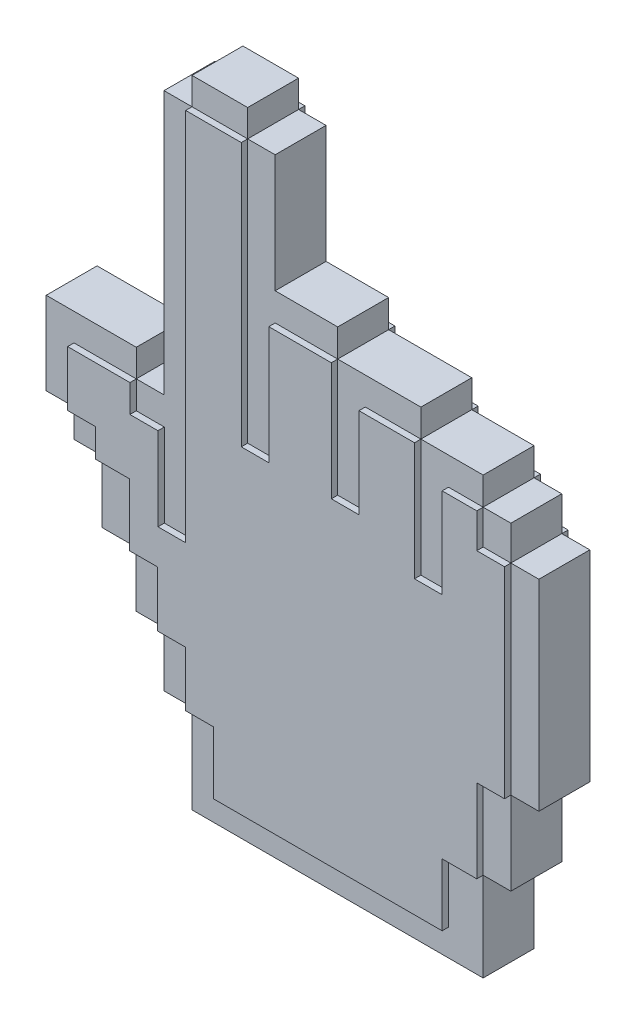
SolidWorks part; units mm, degrees
ref_plane "Front Plane" through (0, 0, 0) normal (0, 0, 1) x (1, 0, 0)
ref_plane "Top Plane" through (0, 0, 0) normal (0, 1, 0) x (1, 0, 0)
ref_plane "Right Plane" through (0, 0, 0) normal (1, 0, 0) x (0, 0, -1)
sketch "Sketch1" plane through (0, 0, 0) normal (0, 0, 1) x (1, 0, 0)
  line L0 (121.3333, 470) -> (606.6667, 470) construction
  line L1 (-21.3493, -53.5319) -> (-21.3493, -35.757)
  line L2 (-21.3493, -35.757) -> (-26.9344, -35.757)
  line L3 (-26.9344, -35.757) -> (-26.9344, -24.7744)
  line L4 (-26.9344, -24.7744) -> (-32.5196, -24.7744)
  line L5 (-32.5196, -24.7744) -> (-32.5196, -13.6979)
  line L6 (-32.5196, -13.6979) -> (-39.3251, -13.6979)
  line L7 (-39.3251, -13.6979) -> (-39.3251, -1.2604)
  line L8 (-39.3251, -1.2604) -> (-44.9102, -1.2604)
  line L9 (-44.9102, -1.2604) -> (-44.9102, 4.3717)
  line L10 (-44.9102, 4.3717) -> (-50.4546, 4.3717)
  line L11 (-50.4546, 4.3717) -> (-50.4546, 20.8885)
  line L12 (-50.4546, 20.8885) -> (-32.4738, 20.8885)
  line L13 (-32.4738, 20.8885) -> (-32.4738, 15.4225)
  line L14 (-32.4738, 15.4225) -> (-26.9344, 15.4225)
  line L15 (-26.9344, 15.4225) -> (-26.9344, 68.0248)
  line L16 (-26.9344, 68.0248) -> (-21.3493, 68.0248)
  line L17 (-21.3493, 68.0248) -> (-21.3493, 73.4488)
  line L18 (-21.3493, 73.4488) -> (-10.2409, 73.4488)
  line L19 (-10.2409, 73.4488) -> (-10.2409, 68.0248)
  line L20 (-10.2409, 68.0248) -> (-4.7518, 68.0248)
  line L21 (-4.7518, 68.0248) -> (-4.7518, 44.5101)
  line L22 (-4.7518, 44.5101) -> (7.7353, 44.5101)
  line L23 (7.7353, 44.5101) -> (7.7353, 38.9478)
  line L24 (7.7353, 38.9478) -> (24.3372, 38.9478)
  line L25 (24.3372, 38.9478) -> (24.3372, 33.4179)
  line L26 (24.3372, 33.4179) -> (36.7659, 33.4179)
  line L27 (36.7659, 33.4179) -> (36.7659, 27.862)
  line L28 (36.7659, 27.862) -> (42.3, 27.862)
  line L29 (42.3, 27.862) -> (42.3, 20.9709)
  line L30 (42.3, 20.9709) -> (47.8955, 20.9709)
  line L31 (47.8955, 20.9709) -> (47.8955, -19.1458)
  line L32 (47.8955, -19.1458) -> (42.3, -19.1458)
  line L33 (42.3, -19.1458) -> (42.3, -35.757)
  line L34 (42.3, -35.757) -> (36.7659, -35.757)
  line L35 (36.7659, -35.757) -> (36.7659, -53.5319)
  line L36 (36.7659, -53.5319) -> (-21.3493, -53.5319)
  line L37 (-15.7951, -48.1996) -> (29.8514, -48.1996)
  line L38 (29.8514, -48.1996) -> (29.8514, -35.757)
  line L39 (29.8514, -35.757) -> (36.7659, -35.757)
  line L40 (36.7659, -19.1458) -> (42.3, -19.1458)
  line L41 (42.3, -19.1458) -> (42.3, 20.9709)
  line L42 (36.7659, 20.9709) -> (36.7659, 27.862)
  line L43 (36.7659, 27.862) -> (29.8514, 27.862)
  line L44 (29.8514, 27.862) -> (29.8514, 9.898)
  line L45 (29.8514, 9.898) -> (24.3372, 9.898)
  line L46 (24.3372, 9.898) -> (24.3372, 33.4179)
  line L47 (24.3372, 33.4179) -> (13.2472, 33.4179)
  line L48 (13.2472, 33.4179) -> (13.2472, 15.4225)
  line L49 (13.2472, 15.4225) -> (7.7353, 15.4225)
  line L50 (7.7353, 15.4225) -> (7.7353, 38.9478)
  line L51 (7.7353, 38.9478) -> (-4.7518, 38.9478)
  line L52 (-4.7518, 38.9478) -> (-4.7518, 15.4225)
  line L53 (-4.7518, 15.4225) -> (-10.2409, 15.4225)
  line L54 (-10.2409, 15.4225) -> (-10.2409, 68.0248)
  line L55 (-21.3493, 68.0248) -> (-21.3493, -6.7133)
  line L56 (-21.3493, -6.7133) -> (-26.8748, -6.7133)
  line L57 (-26.8748, -6.7133) -> (-26.8748, 9.898)
  line L58 (-26.8748, 9.898) -> (-32.4738, 9.898)
  line L59 (-32.4738, 9.898) -> (-32.4738, 15.4225)
  line L60 (-32.4738, 15.4225) -> (-44.9102, 15.4225)
  line L61 (-44.9102, 15.4225) -> (-44.9102, 4.3717)
  line L62 (-44.9102, 4.3717) -> (-39.3251, 4.3717)
  line L63 (-39.3251, 4.3717) -> (-39.3251, -1.2604)
  line L64 (-39.3251, -1.2604) -> (-32.5196, -1.2604)
  line L65 (-32.5196, -1.2604) -> (-32.5196, -13.6979)
  line L66 (-32.5196, -13.6979) -> (-26.9344, -13.6979)
  line L67 (-26.9344, -13.6979) -> (-26.9344, -24.7744)
  line L68 (-26.9344, -24.7744) -> (-21.3493, -24.7744)
  line L69 (-21.3493, -24.7744) -> (-21.3493, -35.757)
  line L70 (-21.3493, -35.757) -> (-15.7951, -35.757)
  line L71 (-15.7951, -35.757) -> (-15.7951, -48.1996)
  line L72 (-21.3493, 68.0248) -> (-10.2409, 68.0248)
  line L73 (36.7659, -19.1458) -> (36.7659, -35.757)
  line L74 (36.7659, 20.9709) -> (42.3, 20.9709)
  point P44 (0, 0)
  dimension "D1" = 7.7353
  dimension "D2" = 13.2472
  dimension "D3" = 24.3372
  dimension "D4" = 29.8514
  dimension "D5" = 36.7659
  dimension "D6" = 42.3
  dimension "D7" = 47.8955
  dimension "D8" = 4.7518
  dimension "D9" = 10.2409
  dimension "D10" = 15.7951
  dimension "D11" = 21.3493
  dimension "D12" = 26.8748
  dimension "D13" = 26.9344
  dimension "D14" = 32.4738
  dimension "D15" = 39.3251
  dimension "D16" = 4.3717
  dimension "D17" = 9.898
  dimension "D18" = 50.4546
  dimension "D19" = 15.4225
  dimension "D20" = 20.8885
  dimension "D21" = 20.9709
  dimension "D22" = 27.862
  dimension "D23" = 33.4179
  dimension "D24" = 38.9478
  dimension "D25" = 44.5101
  dimension "D26" = 68.0248
  dimension "D27" = 73.4488
  dimension "D28" = 470
  dimension "D29" = 1.2604
  dimension "D30" = 6.7133
  dimension "D31" = 13.6979
  dimension "D32" = 19.1458
  dimension "D33" = 24.7744
  dimension "D34" = 35.757
  dimension "D35" = 48.1996
  dimension "D36" = 53.5319
extrude "Boss-Extrude1" add sketch "Sketch1" along normal mid plane 12.7 contours L74 L42 L43 L44 L45 L46 L47 L48 L49 L50 L51 L52 L53 L54 L72 L55 L56 L57 L58 L59 L60 L61 L62 L63 L64 L65 L66 L67 L68 L69 L70 L71 L37 L38 L39 L73 L40 L41 region at (3.6988, -2.9365, 0)
extrude "Boss-Extrude2" add sketch "Sketch1<4>" along normal mid plane 10.16 contours L61 L60 L13 L12 L11 L10 | L63 L62 L9 L8 | L65 L64 L7 L6 | L67 L66 L5 L4 | L69 L68 L3 L2 | L71 L70 L1 L36 L35 L39 L38 L37 | L40 L73 L34 L33 | L41 L32 L31 L30 | L42 L74 L29 L28 | L46 L45 L44 L43 L27 L26 | L50 L49 L48 L47 L25 L24 | L54 L53 L52 L51 L23 L22 L21 L20 | L17 L72 L19 L18 | L59 L58 L57 L56 L55 L16 L15 L14 region at (-20.7415, -44.6445, 0) region at (-24.1419, -30.2657, 0) region at (39.533, -27.4514, 0) region at (-29.727, -19.2362, 0) region at (45.0978, 0.9125, 0) region at (-35.9223, -7.4791, 0) region at (39.533, 24.4165, 0) region at (-42.1176, 1.5557, 0) region at (28.5144, 23.7105, 0) region at (-47.6824, 4.6159, 0) region at (13.1566, 30.0742, 0) region at (-24.5165, 29.4883, 0) region at (-5.7535, 41.7247, 0) region at (-15.7951, 70.7368, 0)
sketch "Sketch1<4>" plane through (0, 0, 0) normal (0, 0, 1) x (1, 0, 0) same geometry as "Sketch1"
